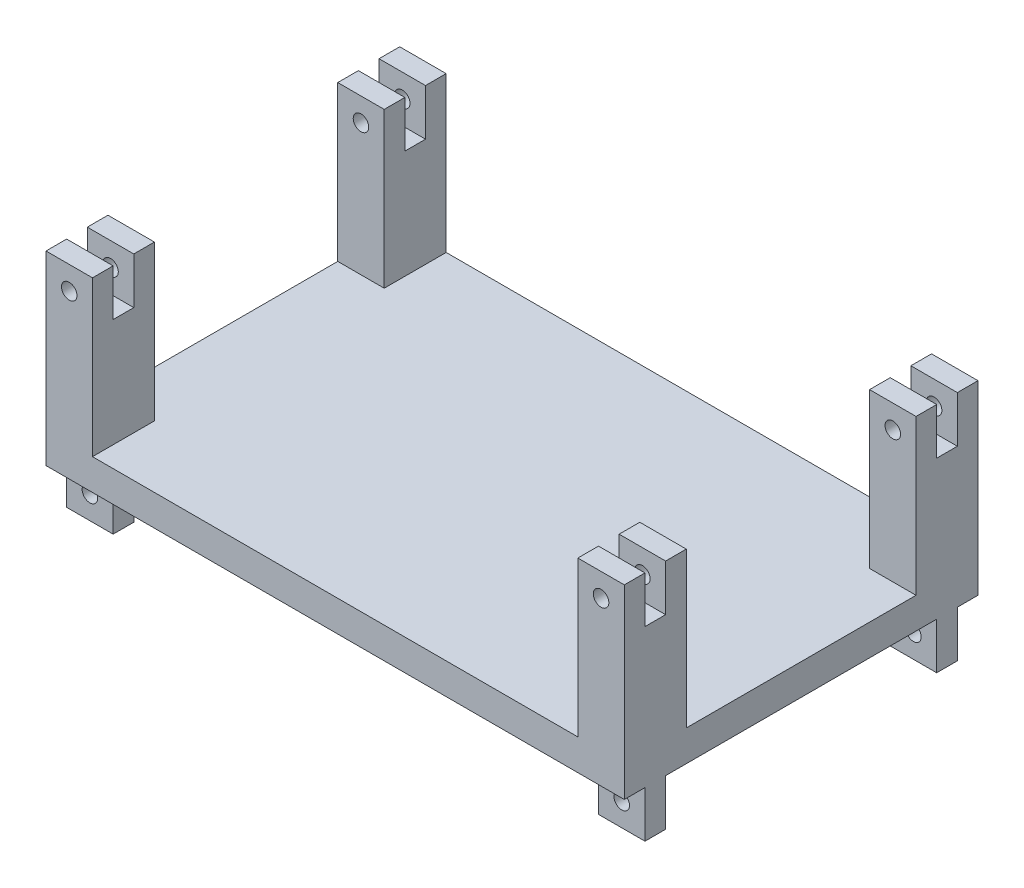
SolidWorks part; units mm, degrees
ref_plane "Front Plane" through (0, 0, 0) normal (0, 0, 1) x (1, 0, 0)
ref_plane "Top Plane" through (0, 0, 0) normal (0, 1, 0) x (1, 0, 0)
ref_plane "Right Plane" through (0, 0, 0) normal (1, 0, 0) x (0, 0, -1)
sketch "Sketch1" plane through (0, 0, 0) normal (0, 1, 0) x (1, 0, 0)
  line L1 (0, 0) -> (-112, 0)
  line L2 (0, 0) -> (0, 34.25)
  line L3 (0, 34.25) -> (-112, 34.25)
  line L4 (-112, 0) -> (-112, 34.25)
  dimension "D1" = 112
  dimension "D2" = 34.25
extrude "Boss-Extrude2" add sketch "Sketch1" along normal blind 6
sketch "Sketch3" plane through (0, 0, 0) normal (0, -1, 0) x (1, 0, 0)
  line L0 (-112, -34.25) -> (-112, 0) construction
  line L1 (-112, -4) -> (-103, -4)
  line L2 (-112, -4) -> (-112, -8)
  line L3 (-112, -8) -> (-103, -8)
  line L4 (-103, -4) -> (-103, -8)
  line L5 (0, 0) -> (0, -34.25) construction
  line L6 (0, -4) -> (-9, -4)
  line L7 (0, -4) -> (0, -8)
  line L8 (0, -8) -> (-9, -8)
  line L9 (-9, -4) -> (-9, -8)
  line L10 (-112, 0) -> (0, 0) construction
  dimension "D1" = 4
  dimension "D2" = 4
  dimension "D3" = 9
  dimension "D4" = 9
  dimension "D5" = 4
  dimension "D6" = 4
extrude "Boss-Extrude3" add sketch "Sketch3" along normal blind 9
sketch "Sketch4" plane through (0, 0, -4) normal (0, 0, 1) x (1, 0, 0)
  line L0 (-112, -9) -> (-112, 0) construction
  line L1 (-103, -9) -> (-112, -9) construction
  line L2 (0, -9) -> (-9, -9) construction
  line L3 (0, -9) -> (0, 0) construction
  circle A0 centre (-107.5, -4.5) radius 1.5
  circle A1 centre (-4.5, -4.5) radius 1.5
  dimension "D1" = 3
  dimension "D2" = 4.5
  dimension "D3" = 4.5
  dimension "D4" = 4.5
  dimension "D5" = 3
  dimension "D6" = 4.5
extrude "Cut-Extrude1" cut sketch "Sketch4" against normal through all
sketch "Sketch5" plane through (0, 6, 0) normal (0, 1, 0) x (1, 0, 0)
  line L1 (-112, 0) -> (-103, 0)
  line L2 (-112, 0) -> (-112, 12)
  line L3 (-112, 12) -> (-103, 12)
  line L4 (-103, 0) -> (-103, 12)
  line L5 (0, 0) -> (-9, 0)
  line L6 (0, 0) -> (0, 12)
  line L7 (0, 12) -> (-9, 12)
  line L8 (-9, 0) -> (-9, 12)
  dimension "D1" = 12
  dimension "D2" = 9
  dimension "D3" = 9
  dimension "D4" = 12
extrude "Boss-Extrude4" add sketch "Sketch5" along normal blind 30
sketch "Sketch6" plane through (0, 36, 0) normal (0, 1, 0) x (1, 0, 0)
  line L0 (-112, 12) -> (-112, 0) construction
  line L1 (-112, 8) -> (-103, 8)
  line L2 (-112, 8) -> (-112, 4)
  line L3 (-112, 4) -> (-103, 4)
  line L4 (-103, 8) -> (-103, 4)
  line L5 (-103, 0) -> (-103, 12) construction
  line L6 (-9, 12) -> (-9, 0) construction
  line L7 (-9, 8) -> (0, 8)
  line L8 (-9, 8) -> (-9, 4)
  line L9 (-9, 4) -> (0, 4)
  line L10 (0, 8) -> (0, 4)
  line L11 (0, 0) -> (0, 12) construction
  line L12 (0, 12) -> (-9, 12) construction
  point P16 (-105.5437, -84.7164)
  dimension "D1" = 4
  dimension "D2" = 4
extrude "Cut-Extrude2" cut sketch "Sketch6" against normal blind 9
sketch "Sketch7" plane through (0, 0, 0) normal (0, 0, 1) x (1, 0, 0)
  line L0 (-112, 36) -> (-112, 0) construction
  line L2 (-112, 36) -> (-103, 36) construction
  line L4 (-9, 36) -> (-9, 6) construction
  circle A0 centre (-107.5, 31.5) radius 1.5
  circle A1 centre (-4.5, 31.5) radius 1.5
  dimension "D1" = 3
  dimension "D2" = 4.5
  dimension "D3" = 4.5
  dimension "D4" = 4.5
extrude "Cut-Extrude3" cut sketch "Sketch7" against normal blind 12
mirror "Mirror1" about plane through (0, 6, -34.25) normal (0, 0, 1) of "Boss-Extrude3", "Cut-Extrude3", "Cut-Extrude2", "Boss-Extrude4", "Cut-Extrude1", "Boss-Extrude2"
